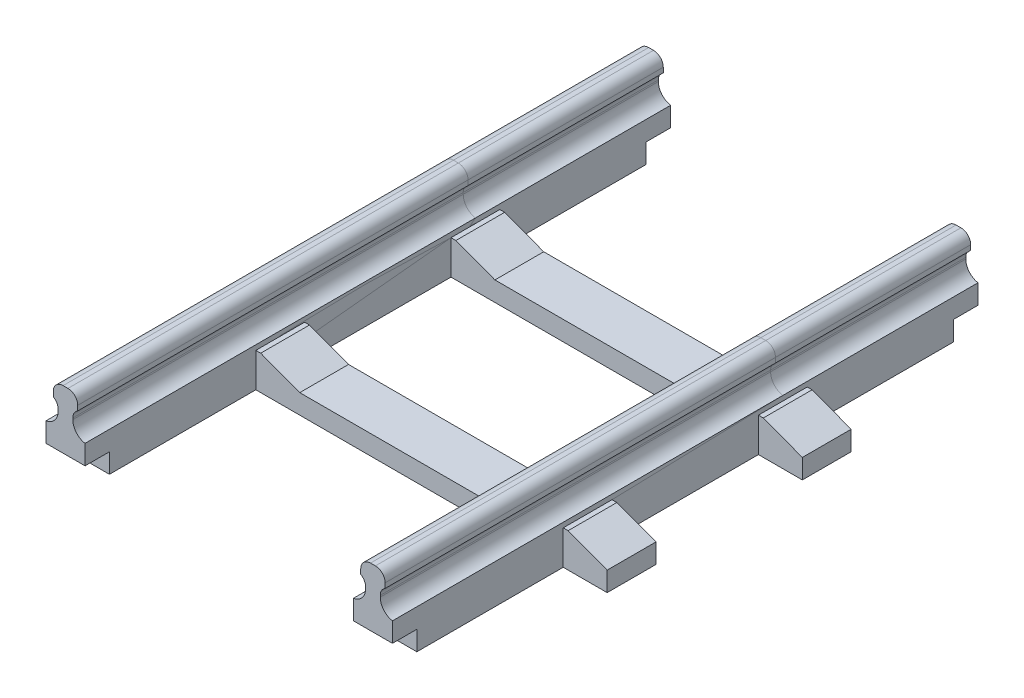
SolidWorks part; units mm, degrees
other "标注1"
sketch "草图3" plane through (-22.25, 4, -10) normal (-0.231, 0.6469, -0.7268) x (-0.9696, -0.2151, 0.1167)
other "标注2"
sketch "草图4" plane through (22.25, 8, -30) normal (0.0083, 0.0567, -0.9984) x (-0.9991, 0.0415, -0.0059)
ref_plane "前视基准面" through (0, 0, 0) normal (0, 0, 1) x (1, 0, 0)
ref_plane "上视基准面" through (0, 0, 0) normal (0, 1, 0) x (1, 0, 0)
ref_plane "右视基准面" through (0, 0, 0) normal (1, 0, 0) x (0, 0, -1)
other "Configuration Table"
sketch "草图1" plane through (0, 0, 0) normal (0, 1, 0) x (1, 0, 0)
  line L0 (-13.75, 11.25) -> (-13.75, -11.25)
  line L13 (-17.75, -11.25) -> (17.75, -11.25)
  line L21 (-17.75, -11.25) -> (-17.75, 11.25)
  line L22 (-17.75, 11.25) -> (17.75, 11.25)
  line L23 (17.75, -11.25) -> (17.75, 11.25)
  line L24 (-17.75, -11.25) -> (17.75, 11.25) construction
  line L25 (-17.75, 11.25) -> (17.75, -11.25) construction
  line L27 (13.75, 11.25) -> (13.75, -11.25)
  line L29 (-13.75, 0) -> (13.75, 0) construction
  line L32 (-22.25, 11.25) -> (22.25, 11.25)
  line L33 (-22.25, 11.25) -> (-22.25, 6.25)
  line L34 (-22.25, 6.25) -> (22.25, 6.25)
  line L35 (22.25, 11.25) -> (22.25, 6.25)
  point P0 (0, 0)
  point P15 (0, 6.25)
  dimension "D3" = 27.5
  dimension "D4" = 5
  dimension "D1" = 35.5
  dimension "D2" = 22.5
  dimension "D5" = 44.5
extrude "凸台-拉伸1" add sketch "草图1" along normal blind 4 contours L34 L21 L13 L0 | L34 L27 L13 L23 | L27 L34 L23 L22 | L21 L34 L0 L22 region at (-15.75, 0, -8.75) region at (-15.75, 0, 2.5) region at (15.75, 0, -8.75) region at (15.75, 0, 2.5)
extrude "凸台-拉伸2" add sketch "草图1<7>" along normal blind 3.5 contours L34 L35 L32 L33
sketch "草图1<7>" plane through (0, 0, 0) normal (0, 1, 0) x (1, 0, 0) same geometry as "草图1"
sketch "草图2" plane through (0, 0, -11.25) normal (0, 0, -1) x (-1, 0, 0)
  line L0 (18.25, 3.5) -> (22.25, 2)
  line L1 (22.25, 3.5) -> (18.25, 3.5)
  line L2 (22.25, 3.5) -> (22.25, 2)
  line L3 (22.25, 2) -> (18.25, 2) construction
  line L4 (18.25, 3.5) -> (18.25, 2) construction
  line L5 (-22.25, 2) -> (-18.25, 3.5)
  line L6 (-22.25, 3.5) -> (-18.25, 3.5)
  line L7 (-22.25, 3.5) -> (-22.25, 2)
  line L8 (-22.25, 2) -> (-18.25, 2) construction
  line L9 (-18.25, 3.5) -> (-18.25, 2) construction
  line L10 (13.75, 3.5) -> (-13.75, 3.5) construction
  line L11 (-13.25, 3.5) -> (-9.25, 3.5)
  line L12 (-13.25, 3.5) -> (-13.25, 2) construction
  line L13 (-13.25, 2) -> (-9.25, 2) construction
  line L14 (-9.25, 3.5) -> (-9.25, 2)
  line L15 (-13.75, 3.5) -> (-13.25, 3.5) construction
  line L16 (13.25, 3.5) -> (9.25, 3.5)
  line L17 (13.25, 3.5) -> (13.25, 2) construction
  line L18 (13.25, 2) -> (9.25, 2) construction
  line L19 (9.25, 3.5) -> (9.25, 2)
  line L20 (13.25, 3.5) -> (13.75, 3.5) construction
  line L21 (17.75, 3.5) -> (18.25, 3.5) construction
  line L22 (-13.25, 3.5) -> (-9.25, 2)
  line L23 (9.25, 2) -> (13.25, 3.5)
  line L24 (-9.25, 2) -> (9.25, 2)
  line L25 (-9.25, 3.5) -> (9.25, 3.5)
  line L26 (-15.75, 4) -> (-15.75, 6.5) construction
  line L27 (14.5, 8) -> (17, 8)
  line L28 (14.5, 8) -> (14.5, 6.5)
  line L29 (14.5, 6.5) -> (17, 6.5)
  line L30 (17, 8) -> (17, 6.5)
  line L31 (-17, 8) -> (-14.5, 8)
  line L32 (-17, 8) -> (-17, 6.5)
  line L33 (-17, 6.5) -> (-14.5, 6.5)
  line L34 (-14.5, 8) -> (-14.5, 6.5)
  line L35 (-13.75, 4) -> (-17.75, 4) construction
  line L36 (15.75, 6.5) -> (15.75, 4) construction
  line L37 (17.75, 4) -> (13.75, 4) construction
  line L38 (15, 6.5) -> (15, 4)
  line L39 (16.5, 6.5) -> (16.5, 4)
  line L40 (16.5, 4) -> (15.75, 4)
  line L41 (15.75, 4) -> (15, 4)
  line L42 (-16.5, 6.5) -> (-16.5, 4)
  line L43 (-16.5, 4) -> (-15.75, 4)
  line L44 (-15.75, 4) -> (-15, 4)
  line L45 (-15, 4) -> (-15, 6.5)
  line M9 (22.25, 3.5) -> (17.75, 3.5)
  line M11 (17.75, 4) -> (13.75, 4)
  line M13 (13.75, 3.5) -> (-13.75, 3.5)
  line M15 (-13.75, 4) -> (-17.75, 4)
  line M17 (-17.75, 3.5) -> (-22.25, 3.5)
  line M18 (-22.25, 3.5) -> (-22.25, 0)
  line M20 (22.25, 0) -> (22.25, 3.5)
  dimension "D1" = 4
  dimension "D2" = 1.5
  dimension "D3" = 2.5
  dimension "D4" = 1.5
  dimension "D5" = 2.5
  dimension "D6" = 1.5
extrude "切除-拉伸1" cut sketch "草图2" against normal through all contours L14 L24 L19 M13 | L19 L23 M13 | L22 L14 M13 | L5 M18 M17 | L0 M9 M20 region at (-20.9167, 3, -11.25) region at (20.9167, 3, -11.25) region at (10.5833, 3, -11.25) region at (0, 2.75, -11.25) region at (-10.5833, 3, -11.25)
extrude "凸台-拉伸4" add sketch "草图2<3>" against normal through all contours L34 L31 L32 L33 | L45 L33 L42 M15 | L30 L27 L28 L29 | L39 L29 L38 M11 region at (-15.75, 7.25, -11.25) region at (-15.75, 5.25, -11.25) region at (15.75, 7.25, -11.25) region at (15.75, 5.25, -11.25)
sketch "草图2<3>" plane through (0, 0, -11.25) normal (0, 0, -1) x (-1, 0, 0) same geometry as "草图2"
fillet "圆角1" radius 1 4 edges at (-16.5, 6.5, 0) (-15, 6.5, 0) (15, 6.5, 0) (16.5, 6.5, 0)
fillet "圆角2" radius 1.5 4 edges at (16.5, 4, 0) (15, 4, 0) (-15, 4, 0) (-16.5, 4, 0)
fillet "圆角3" radius 1 4 edges at (-17, 8, 0) (14.5, 8, 0) (17, 8, 0) (-14.5, 8, 0)
sketch "草图5" plane through (17.75, 0, 0) normal (1, 0, 0) x (0, 0, -1)
  line L0 (-11.25, 4) -> (-11.25, 0) construction
  line L1 (-11.25, 2) -> (-8.75, 2)
  line L2 (-11.25, 2) -> (-11.25, 0)
  line L3 (-11.25, 0) -> (-8.75, 0)
  line L4 (-8.75, 2) -> (-8.75, 0)
  line L5 (-11.25, 0) -> (6.25, 0) construction
  dimension "D1" = 2.5
  dimension "D2" = 2
extrude "切除-拉伸2" cut sketch "草图5" against normal through all
sketch "草图10" plane through (0, 2, 0) normal (0, -1, 0) x (1, 0, 0)
  line L0 (13.75, 11.25) -> (17.75, 8.75) construction
  line L1 (13.75, 11.25) -> (17.75, 11.25) construction
  line L2 (13.75, 8.75) -> (13.75, 11.25) construction
  line L3 (13.75, 8.75) -> (17.75, 8.75) construction
  line L4 (17.75, 8.75) -> (17.75, 11.25) construction
  line L5 (-17.75, 11.25) -> (-13.75, 8.75) construction
  line L6 (-17.75, 11.25) -> (-17.75, 8.75) construction
  line L7 (-17.75, 11.25) -> (-13.75, 11.25) construction
  line L8 (-13.75, -6.25) -> (-13.75, 8.75) construction
  line L9 (-17.75, 8.75) -> (-13.75, 8.75) construction
  circle A0 centre (15.75, 10) radius 0.4
  circle A1 centre (-15.75, 10) radius 0.4
  dimension "D1" = 0.8
extrude "切除-拉伸3" cut sketch "草图10" against normal blind 2
sketch "草图8" plane through (22.25, 0, 0) normal (1, 0, 0) x (0, 0, -1)
  line L0 (8.75, 0) -> (8.75, 18.5305)
  line L1 (11.25, 0) -> (6.25, 0) construction
ref_plane "基准面1" through (0, 0, -8.75) normal (0, 0, -1) x (-1, 0, 0)
mirror "镜向1" about plane through (0, 0, -8.75) normal (0, 0, -1) of bodies 202 196
pattern_linear "阵列(线性)2" count 2 spacing 20 along (0, 0, -1) of bodies 197 192
